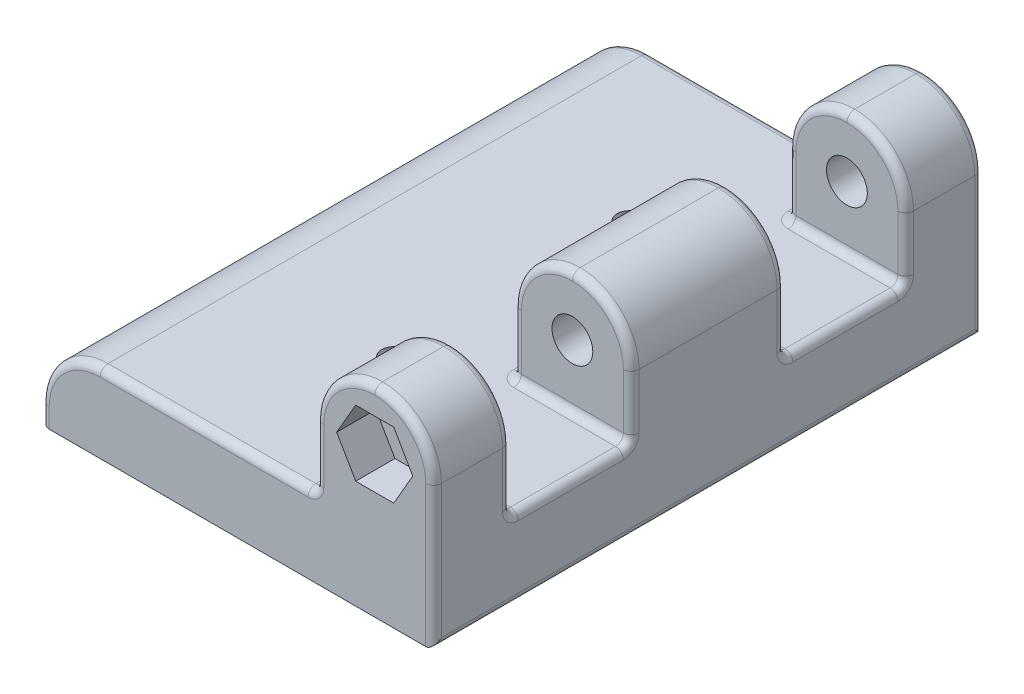
SolidWorks part; units mm, degrees
ref_plane "Front Plane" through (0, 0, 0) normal (0, 0, 1) x (1, 0, 0)
ref_plane "Top Plane" through (0, 0, 0) normal (0, 1, 0) x (1, 0, 0)
ref_plane "Right Plane" through (0, 0, 0) normal (1, 0, 0) x (0, 0, -1)
sketch "Sketch1" plane through (0, 0, 0) normal (0, 1, 0) x (1, 0, 0)
  line L0 (25, -35) -> (25, 35)
  line L1 (-25, 35) -> (25, 35)
  line L2 (-25, 35) -> (-25, -35)
  line L3 (-25, -35) -> (25, -35)
  line L4 (25, 35) -> (25, -35)
  line L5 (-25, 35) -> (25, -35) construction
  line L6 (-25, -35) -> (25, 35) construction
  point P0 (0, 0)
  dimension "D1" = 70
  dimension "D2" = 50
extrude "Boss-Extrude1" add sketch "Sketch1" along normal blind 10 contours L2 L3 L0 L1 | L4 L0 | L4 | L4 L0 | L4 region at (0, 0, 0)
sketch "Sketch4" plane through (0, 10, 0) normal (0, 1, 0) x (1, 0, 0)
  line L0 (25, -35) -> (25, 35) construction
  line L1 (25, 35) -> (10, 35)
  line L2 (25, 35) -> (25, 25.2)
  line L3 (25, 25.2) -> (10, 25.2)
  line L4 (10, 35) -> (10, 25.2)
  line L5 (25, -35) -> (10, -35)
  line L6 (25, -35) -> (25, -25.2)
  line L7 (25, -25.2) -> (10, -25.2)
  line L8 (10, -35) -> (10, -25.2)
  line L9 (25, -9.8) -> (10, -9.8)
  line L10 (25, -9.8) -> (25, 9.8)
  line L11 (25, 9.8) -> (10, 9.8)
  line L12 (10, -9.8) -> (10, 9.8)
  dimension "D1" = 9.8
  dimension "D2" = 9.8
  dimension "D3" = 15
  dimension "D4" = 15
  dimension "D5" = 15
  dimension "D6" = 15.4
  dimension "D7" = 15.4
extrude "Boss-Extrude2" add sketch "Sketch4" along normal blind 15.5
sketch "Sketch5" plane through (0, 0, 35) normal (0, 0, 1) x (1, 0, 0)
  line L0 (10, 25.5) -> (25, 25.5) construction
  line L1 (25, 25.5) -> (25, 0) construction
  circle A0 centre (17.5, 18) radius 2.6
  dimension "D1" = 5.2
  dimension "D2" = 7.5
  dimension "D3" = 7.5
extrude "Cut-Extrude1" cut sketch "Sketch5" against normal through all
fillet "Fillet1" radius 7.5 6 edges at (10, 25.5, -30.1) (10, 25.5, 0) (10, 25.5, 30.1) (25, 25.5, 30.1) (25, 25.5, 0) (25, 25.5, -30.1)
sketch "Sketch6" plane through (0, 0, 35) normal (0, 0, 1) x (1, 0, 0)
  line L0 (-25, 0) -> (25, 0) construction
  line L1 (19.9249, 13.8) -> (22.3497, 18)
  line L2 (22.3497, 18) -> (19.9249, 22.2)
  line L3 (19.9249, 22.2) -> (15.0751, 22.2)
  line L4 (15.0751, 22.2) -> (12.6503, 18)
  line L5 (12.6503, 18) -> (15.0751, 13.8)
  line L6 (15.0751, 13.8) -> (19.9249, 13.8)
  circle A1 centre (17.5, 18) radius 4.2 construction
  dimension "D2" = 8.4
extrude "Cut-Extrude2" cut sketch "Sketch6" against normal blind 5
sketch "Sketch7" plane through (0, 0, -35) normal (0, 0, -1) x (-1, 0, 0)
  circle A0 centre (-17.5, 18) radius 5.1
  arc A1 (-10, 18) -> (-17.5, 25.5) centre (-17.5, 18) ccw construction
  dimension "D1" = 10.2
extrude "Cut-Extrude3" cut sketch "Sketch7" against normal blind 5
fillet "Fillet2" radius 7.5 1 edges at (-25, 10, 0)
sketch "Sketch8" plane through (0, 10, 0) normal (0, 1, 0) x (1, 0, 0)
  line L1 (-17.5, 35) -> (10, 35) construction
  line L9 (-17.5, -35) -> (10, -35) construction
  line L11 (25, 9.8) -> (25, 25.2) construction
  line L12 (25, -25.2) -> (25, -9.8) construction
  circle A0 centre (0, 15) radius 1.6
  circle A1 centre (0, -15) radius 1.6
  point P8 (-3.75, -35)
  dimension "D1" = 3.2
  dimension "D2" = 3.2
  dimension "D3" = 20
  dimension "D4" = 20
  dimension "D5" = 25
  dimension "D6" = 25
extrude "Cut-Extrude4" cut sketch "Sketch8" against normal blind 5
fillet "Fillet3" radius 1 40 edges at (17.5, 10, 9.8) (10, 10, -30.1) (10, 10, 0) (10, 10, 30.1) (25, 14, -25.2) (10, 14, -25.2) (12.1967, 23.3033, -25.2) (10, 14, -9.8) (12.1967, 23.3033, -9.8) (22.8033, 23.3033, -9.8) (10, 14, 35) (12.1967, 23.3033, 35) (22.8033, 23.3033, 35) (10, 14, 25.2) (12.1967, 23.3033, 25.2) (22.8033, 23.3033, 25.2) (10, 14, 9.8) (12.1967, 23.3033, 9.8) (22.8033, 23.3033, 9.8) (10, 14, -35) (12.1967, 23.3033, -35) (22.8033, 23.3033, -35) (-25, 1.25, 35) (-22.8033, 7.8033, 35) (-25, 1.25, -35) (-22.8033, 7.8033, -35) (17.5, 10, -25.2) (22.8033, 23.3033, -25.2) (17.5, 10, 25.2) (17.5, 10, -9.8) (25, 14, -9.8) (25, 9, 35) (25, 14, 25.2) (25, 14, 9.8) (25, 10, 17.5) (25, 10, -17.5) (25, 0, 0) (25, 9, -35) (-3.75, 10, 35) (-3.75, 10, -35)
